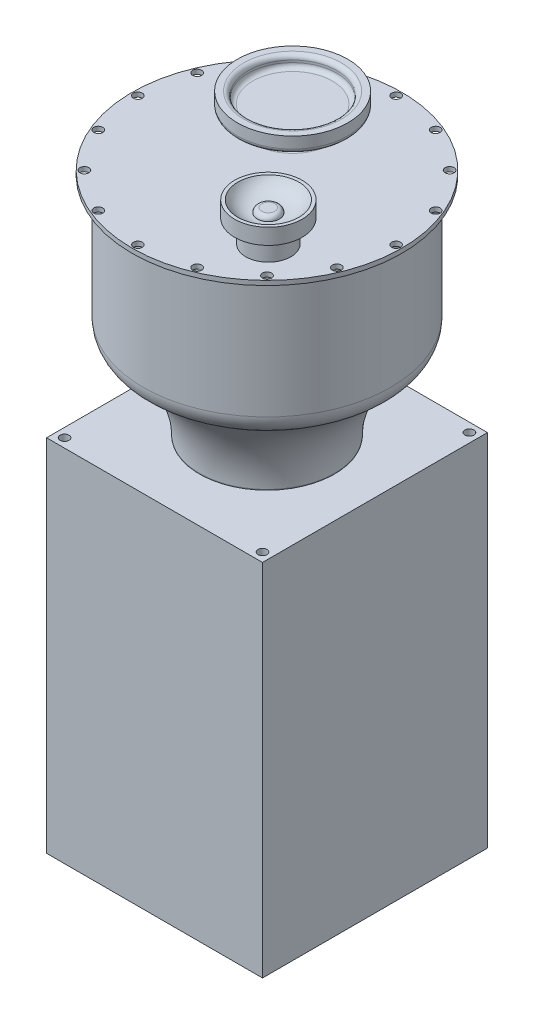
SolidWorks part; units mm, degrees
material "ABS"
ref_plane "Front Plane" through (0, 0, 0) normal (0, 0, 1) x (1, 0, 0)
ref_plane "Top Plane" through (0, 0, 0) normal (0, 1, 0) x (1, 0, 0)
ref_plane "Right Plane" through (0, 0, 0) normal (1, 0, 0) x (0, 0, -1)
sketch "Sketch1" plane through (0, 0, 0) normal (0, 1, 0) x (1, 0, 0)
  line L1 (-60.96, -63.5) -> (60.96, -63.5)
  line L2 (-60.96, -63.5) -> (-60.96, 63.5)
  line L3 (-60.96, 63.5) -> (60.96, 63.5)
  line L4 (60.96, -63.5) -> (60.96, 63.5)
  line L5 (-60.96, -63.5) -> (60.96, 63.5) construction
  line L6 (-60.96, 63.5) -> (60.96, -63.5) construction
  point P0 (0, 0)
  dimension "D1" = 121.92
  dimension "D2" = 127
extrude "Boss-Extrude1" add sketch "Sketch1" along normal blind 203.2
sketch "Sketch2" plane through (0, 203.2, 0) normal (0, 1, 0) x (1, 0, 0)
  circle A0 centre (0, 0) radius 38.1
  dimension "D1" = 76.2
extrude "Boss-Extrude2" add sketch "Sketch2" along normal blind 50.8
sketch "Sketch3" plane through (0, 254, 0) normal (0, 1, 0) x (1, 0, 0)
  circle A0 centre (0, 0) radius 69.85
  dimension "D1" = 139.7
extrude "Boss-Extrude3" add sketch "Sketch3" along normal blind 76.2
fillet "Fillet1" radius 55.88 1 edges at (0, 254, 38.1)
fillet "Fillet2" radius 12.7 1 edges at (0, 254, 69.85)
sketch "Sketch4" plane through (0, 330.2, 0) normal (0, 1, 0) x (1, 0, 0)
  circle A0 centre (0, 0) radius 63.5
  dimension "D1" = 127
extrude "Cut-Extrude1" cut sketch "Sketch4" against normal blind 76.2 draft 9
fillet "Fillet3" radius 12.7 1 edges at (0, 254, 51.4311)
sketch "Sketch5" plane through (0, 330.2, 0) normal (0, 1, 0) x (1, 0, 0)
  circle A0 centre (0, 0) radius 76.2
  dimension "D1" = 152.4
extrude "Boss-Extrude4" add sketch "Sketch5" along normal blind 2.54
sketch "Sketch6" plane through (0, 332.74, 0) normal (0, 1, 0) x (1, 0, 0)
  circle A0 centre (0, 0) radius 72.898 construction
  circle A1 centre (0, 72.898) radius 2.54
  circle A2 centre (0, 0) radius 72.898 construction
  circle A3 centre (27.8969, 67.349) radius 2.54
  circle A4 centre (0, 0) radius 72.898 construction
  circle A5 centre (51.5467, 51.5467) radius 2.54
  circle A6 centre (0, 0) radius 72.898 construction
  circle A7 centre (67.349, 27.8969) radius 2.54
  circle A8 centre (0, 0) radius 72.898 construction
  circle A9 centre (72.898, 0) radius 2.54
  circle A10 centre (0, 0) radius 72.898 construction
  circle A11 centre (67.349, -27.8969) radius 2.54
  circle A12 centre (0, 0) radius 72.898 construction
  circle A13 centre (51.5467, -51.5467) radius 2.54
  circle A14 centre (0, 0) radius 72.898 construction
  circle A15 centre (27.8969, -67.349) radius 2.54
  circle A16 centre (0, 0) radius 72.898 construction
  circle A17 centre (0, -72.898) radius 2.54
  circle A18 centre (0, 0) radius 72.898 construction
  circle A19 centre (-27.8969, -67.349) radius 2.54
  circle A20 centre (0, 0) radius 72.898 construction
  circle A21 centre (-51.5467, -51.5467) radius 2.54
  circle A22 centre (0, 0) radius 72.898 construction
  circle A23 centre (-67.349, -27.8969) radius 2.54
  circle A24 centre (0, 0) radius 72.898 construction
  circle A25 centre (-72.898, 0) radius 2.54
  circle A26 centre (0, 0) radius 72.898 construction
  circle A27 centre (-67.349, 27.8969) radius 2.54
  circle A28 centre (0, 0) radius 72.898 construction
  circle A29 centre (-51.5467, 51.5467) radius 2.54
  circle A30 centre (0, 0) radius 72.898 construction
  circle A31 centre (-27.8969, 67.349) radius 2.54
  point P52 (0, 0)
  dimension "D1" = 5.08
  dimension "D3" = 145.796
  dimension "D2" = 16
extrude "Cut-Extrude2" cut sketch "Sketch6" against normal blind 2.54
sketch "Sketch8" plane through (0, 332.74, 0) normal (0, 1, 0) x (1, 0, 0)
  circle A0 centre (36.3938, -35.6195) radius 12.7
  dimension "D1" = 25.4
extrude "Boss-Extrude5" add sketch "Sketch8" along normal blind 12.7
sketch "Sketch9" plane through (0, 345.44, 0) normal (0, 1, 0) x (1, 0, 0)
  circle A0 centre (36.3938, -35.6195) radius 19.05
  dimension "D1" = 38.1
extrude "Boss-Extrude6" add sketch "Sketch9" along normal blind 8.89
sketch "Sketch10" plane through (0, 354.33, 0) normal (0, 1, 0) x (1, 0, 0)
  circle A0 centre (36.3938, -35.6195) radius 17.2278
extrude "Cut-Extrude9" cut sketch "Sketch10" against normal blind 6.35
fillet "Fillet4" radius 12.7 1 edges at (36.3938, 347.98, 52.8473)
sketch "Sketch11" plane through (0, 347.98, 0) normal (0, 1, 0) x (1, 0, 0)
  circle A0 centre (36.3938, -35.6195) radius 6.2293
extrude "Boss-Extrude7" add sketch "Sketch11" along normal blind 2.54
fillet "Fillet5" radius 2.54 1 edges at (36.3938, 350.52, 41.8488)
sketch "Sketch12" plane through (0, 332.74, 0) normal (0, 1, 0) x (1, 0, 0)
  circle A0 centre (-16.2611, 30.7154) radius 19.05
  dimension "D1" = 38.1
extrude "Boss-Extrude8" add sketch "Sketch12" along normal blind 6.35
sketch "Sketch13" plane through (0, 339.09, 0) normal (0, 1, 0) x (1, 0, 0)
  circle A0 centre (-16.2611, 30.7154) radius 31.1643
extrude "Boss-Extrude9" add sketch "Sketch13" along normal blind 8.89
sketch "Sketch14" plane through (0, 347.98, 0) normal (0, 1, 0) x (1, 0, 0)
  circle A0 centre (-16.2611, 30.7154) radius 25.0369
extrude "Cut-Extrude11" cut sketch "Sketch14" against normal blind 6.35
fillet "Fillet6" radius 2.54 1 edges at (-16.2611, 341.63, -5.6785)
fillet "Fillet7" radius 2.54 1 edges at (-16.2611, 347.98, -5.6785)
fillet "Fillet8" radius 2.54 1 edges at (-16.2611, 332.74, -11.6654)
fillet "Fillet9" radius 2.54 1 edges at (-16.2611, 339.09, -11.6654)
fillet "Fillet10" radius 2.54 1 edges at (-16.2611, 339.09, 0.449)
sketch "Sketch15" plane through (0, 0, 0) normal (0, -1, 0) x (1, 0, 0)
  line L8 (55.88, -58.42) -> (55.88, 58.42)
  line L9 (55.88, 58.42) -> (-55.88, 58.42)
  line L10 (-55.88, 58.42) -> (-55.88, -58.42)
  line L11 (-55.88, -58.42) -> (55.88, -58.42)
  line L12 (55.88, -58.42) -> (55.88, 58.42)
  line L13 (55.88, 58.42) -> (-55.88, 58.42)
  line L14 (-55.88, 58.42) -> (-55.88, -58.42)
  line L15 (-55.88, -58.42) -> (55.88, -58.42)
  circle A0 centre (-55.88, 58.42) radius 2.54
  circle A1 centre (55.88, 58.42) radius 2.54
  circle A2 centre (-55.88, -58.42) radius 2.54
  circle A3 centre (55.88, -58.42) radius 2.54
  dimension "D2" = 5.08
  dimension "D3" = 5.08
  dimension "D4" = 5.08
  dimension "D5" = 5.08
  dimension "D1" = 5.08
extrude "Cut-Extrude12" cut sketch "Sketch15" against normal up to surface (203.2 mm away) contours L12 A1 L13 | L13 A1 L12 | L13 A0 L14 | L14 A0 L13 | L15 A2 L14 | L14 A2 L15 | L12 A3 L15 | L15 A3 L12 region at (54.802, 0, -57.342) region at (56.2393, 0, -58.7793) region at (54.802, 0, 57.342) region at (56.2393, 0, 58.7793) region at (-56.2393, 0, -58.7793) region at (-54.802, 0, -57.342) region at (-54.802, 0, 57.342) region at (-56.2393, 0, 58.7793) up to face at (0, 203.2, -38.1)
